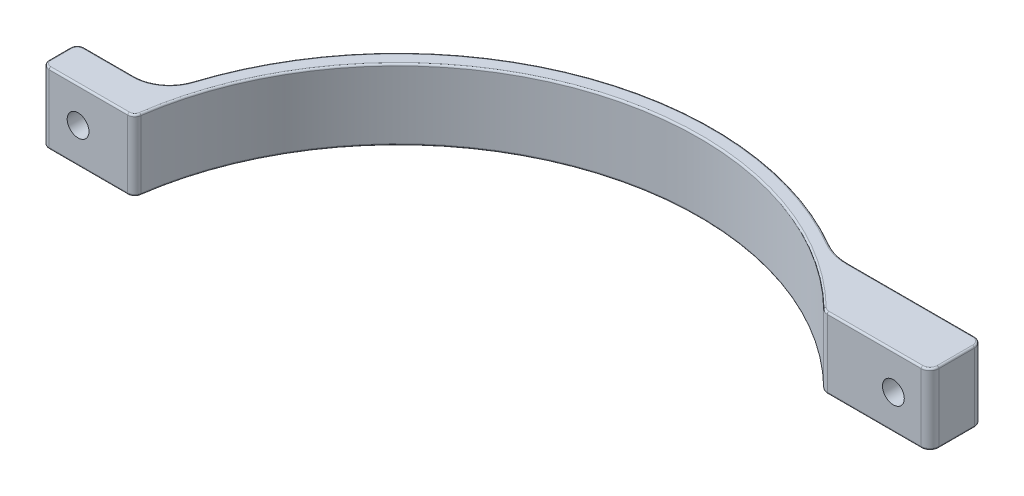
SolidWorks part; units mm, degrees
material "PVC 0.007 Plasticizado"
ref_plane "Plano frontal" through (0, 0, 0) normal (0, 0, 1) x (1, 0, 0)
ref_plane "Plano superior" through (0, 0, 0) normal (0, 1, 0) x (1, 0, 0)
ref_plane "Plano direito" through (0, 0, 0) normal (1, 0, 0) x (0, 0, -1)
sketch "Esboço1" plane through (0, 0, 0) normal (0, 1, 0) x (1, 0, 0)
  line L0 (0, -1000) -> (0, 49000) construction
  line L1 (-1000, 0) -> (49000, 0) construction
  line L3 (61.2372, 60) -> (87.708, 60)
  line L4 (90.208, 62.5) -> (90.208, 72.5)
  line L5 (87.708, 75) -> (52.1153, 75)
  line L7 (-108.4097, 20) -> (-94.3451, 20)
  line L8 (-110.4097, 18) -> (-110.4097, 12)
  line L9 (-108.4097, 10) -> (-86.1684, 10)
  arc A0 (59.4876, 60.7143) -> (-84.1876, 11.7241) centre (0, 0) ccw
  arc A1 (44.5986, 77.0192) -> (-84.8153, 26.9697) centre (0, 0) ccw
  circle A2 centre (0, 0) radius 85 construction
  circle A3 centre (0, 0) radius 89 construction
  arc A4 (44.5986, 77.0192) -> (52.1153, 75) centre (52.1153, 90) ccw
  arc A5 (90.208, 72.5) -> (87.708, 75) centre (87.708, 72.5) ccw
  arc A6 (87.708, 60) -> (90.208, 62.5) centre (87.708, 62.5) ccw
  arc A7 (59.4876, 60.7143) -> (61.2372, 60) centre (61.2372, 62.5) ccw
  arc A11 (-94.3451, 20) -> (-84.8153, 26.9697) centre (-94.3451, 30) ccw
  arc A12 (-84.1876, 11.7241) -> (-86.1684, 10) centre (-86.1684, 12) cw
  arc A13 (-108.4097, 10) -> (-110.4097, 12) centre (-108.4097, 12) cw
  arc A14 (-108.4097, 20) -> (-110.4097, 18) centre (-108.4097, 18) ccw
  point P9 (-177.2056, 15)
  point P25 (90.208, 75)
  point P28 (90.208, 60)
  point P31 (60.208, 60)
  point P34 (-84.4097, 10)
  point P37 (-110.4097, 10)
  point P49 (-110.4097, 10)
  dimension "D1" = 4
  dimension "D4" = 170
  dimension "D5" = 60
  dimension "D8" = 15
  dimension "D9" = 2.5
  dimension "D10" = 2
  dimension "D11" = 10
  dimension "D13" = 2
  dimension "D14" = 2
  dimension "D2" = 26
  dimension "D3" = 15
  dimension "D6" = 30
  dimension "D7" = 10
  dimension "D12" = 10
extrude "Ressalto-extrusão1" add sketch "Esboço1" along normal blind 20
sketch "Esboço3" plane through (0, 0, -60) normal (0, 0, 1) x (1, 0, 0)
  line L1 (61.2372, 20) -> (59.4876, 20) construction
  circle A0 centre (79.8624, 9.7994) radius 3.075
  point P4 (60.3624, 20)
  dimension "D1" = 19.5
extrude "Corte-extrusão1" cut sketch "Esboço3" against normal blind 20
sketch "Esboço4" plane through (0, 0, -75) normal (0, 0, -1) x (-1, 0, 0)
  circle A0 centre (-79.8624, 9.7994) radius 5.25
extrude "Corte-extrusão2" cut sketch "Esboço4" against normal blind 6
sketch "Esboço5" plane through (0, 0, -10) normal (0, 0, 1) x (1, 0, 0)
  line L0 (-108.4097, 20) -> (-86.1684, 20) construction
  line L5 (-108.4097, 20) -> (-108.4097, 0) construction
  circle A0 centre (-100.1797, 10) radius 3.075
  dimension "D1" = 6.15
  dimension "D2" = 10
  dimension "D3" = 8.23
extrude "Corte-extrusão3" cut sketch "Esboço5" against normal through all and the other way through all
sketch "Esboço6" plane through (0, 0, -20) normal (0, 0, -1) x (-1, 0, 0)
  line L1 (105.2047, 7.0988) -> (105.2047, 12.9012)
  line L2 (105.2047, 12.9012) -> (100.1797, 15.8024)
  line L3 (100.1797, 15.8024) -> (95.1547, 12.9012)
  line L4 (95.1547, 12.9012) -> (95.1547, 7.0988)
  line L5 (95.1547, 7.0988) -> (100.1797, 4.1976)
  line L6 (100.1797, 4.1976) -> (105.2047, 7.0988)
  circle A0 centre (100.1797, 10) radius 5.025 construction
  dimension "D1" = 10.05
extrude "Corte-extrusão4" cut sketch "Esboço6" against normal blind 5
fillet "Filete1" radius 0.5 32 edges at (-32.1027, 0, -83.0085) (-88.4419, 0, -21.9284) (-101.3774, 0, -20) (-109.8239, 0, -19.4142) (-110.4097, 0, -15) (-109.8239, 0, -10.5858) (-97.2891, 0, -10) (-84.8554, 0, -10.4914) (-27.4323, 0, -80.4517) (60.2923, 0, -60.1854) (74.4726, 0, -60) (89.4757, 0, -60.7322) (90.208, 0, -67.5) (89.4757, 0, -74.2678) (69.9116, 0, -75) (48.2237, 0, -75.5136) (69.9116, 20, -75) (89.4757, 20, -74.2678) (90.208, 20, -67.5) (89.4757, 20, -60.7322) (74.4726, 20, -60) (60.2923, 20, -60.1854) (-27.4323, 20, -80.4517) (-84.8554, 20, -10.4914) (-97.2891, 20, -10) (-109.8239, 20, -10.5858) (-110.4097, 20, -15) (-109.8239, 20, -19.4142) (-101.3774, 20, -20) (-88.4419, 20, -21.9284) (-32.1027, 20, -83.0085) (48.2237, 20, -75.5136)
